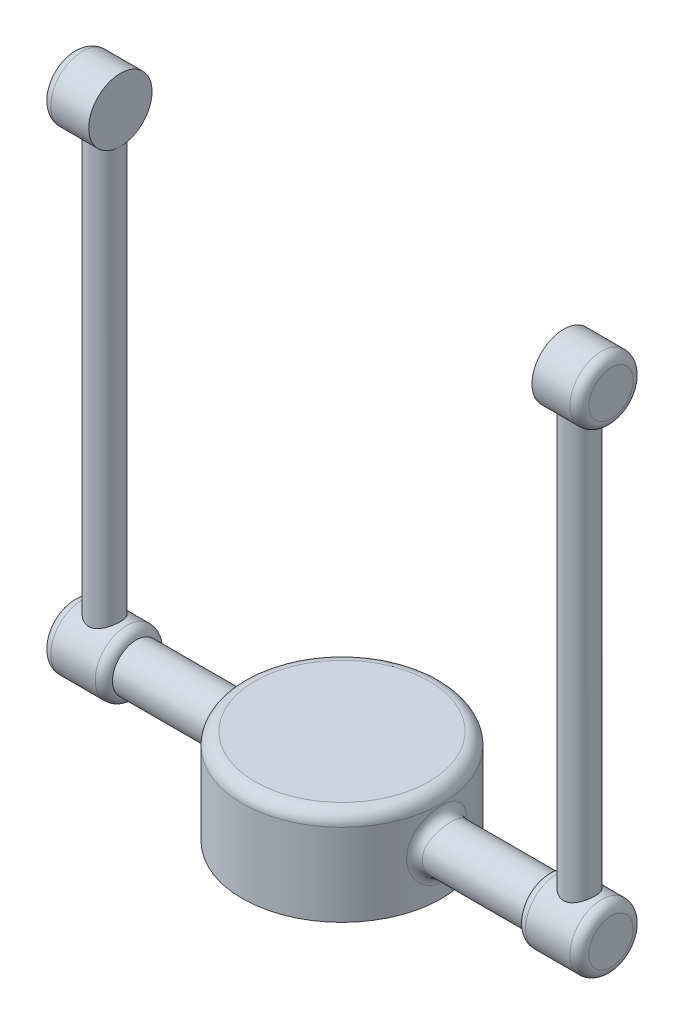
SolidWorks part; units mm, degrees
material "Polyester Resin"
ref_plane "Front Plane" through (0, 0, 0) normal (0, 0, 1) x (1, 0, 0)
ref_plane "Top Plane" through (0, 0, 0) normal (0, 1, 0) x (1, 0, 0)
ref_plane "Right Plane" through (0, 0, 0) normal (1, 0, 0) x (0, 0, -1)
sketch "Sketch1" plane through (0, 0, 0) normal (0, 1, 0) x (1, 0, 0)
  circle A0 centre (0, 0) radius 31.5
  dimension "D1" = 63
extrude "Boss-Extrude1" add sketch "Sketch1" along normal blind 30
sketch "Sketch2" plane through (0, 0, 0) normal (1, 0, 0) x (0, 0, -1)
  line L0 (0, 0) -> (0, 30) construction
  line L1 (31.5, 30) -> (-31.5, 30) construction
  circle A0 centre (0, 15) radius 7.5
  dimension "D1" = 15
extrude "Boss-Extrude2" add sketch "Sketch2" along normal blind 65
sketch "Sketch3" plane through (65, 0, 0) normal (1, 0, 0) x (0, 0, -1)
  circle A0 centre (0, 15) radius 10
  dimension "D1" = 20
extrude "Boss-Extrude3" add sketch "Sketch3" along normal blind 20
ref_axis "Axis1" through (0, 15, 0) along (1, 0, 0)
ref_plane "Plane1" through (0, 15, 0) normal (0, -1, 0) x (1, 0, 0)
sketch "Sketch4" plane through (0, 15, 0) normal (0, -1, 0) x (1, 0, 0)
  line L0 (0, 0) -> (65, 0) construction
  line L2 (65, 10) -> (65, -10) construction
  circle A0 centre (75, 0) radius 5
  dimension "D1" = 10
  dimension "D2" = 10
extrude "Boss-Extrude4" add sketch "Sketch4" against normal blind 150
sketch "Sketch5" plane through (85, 0, 0) normal (1, 0, 0) x (0, 0, -1)
  line L0 (0, 165) -> (0, 15) construction
  line L1 (5, 165) -> (-5, 165) construction
  circle A0 centre (0, 165) radius 10
  dimension "D1" = 20
extrude "Boss-Extrude5" add sketch "Sketch5" against normal blind 15
fillet "Fillet1" radius 3 4 edges at (30.6305, 16.492, -7.3501) (65, 15, -10) (85, 15, -10) (85, 165, -10)
mirror "Mirror1" about plane through (0, 0, 0) normal (1, 0, 0) of "Boss-Extrude5", "Boss-Extrude2", "Fillet1", "Boss-Extrude4", "Boss-Extrude3"
fillet "Fillet2" radius 4 1 edges at (0, 30, 31.5)
sketch "Sketch7" plane through (0, 0, 0) normal (0, 0, 1) x (1, 0, 0)
  line L0 (0, 0) -> (0, 10) construction
  line L2 (-12.5, 10) -> (12.5, 10) construction
  circle A1 centre (-12.5, 10) radius 4
  circle A2 centre (12.5, 10) radius 4
  point P6 (0, 10)
  dimension "D1" = 25
  dimension "D2" = 8
  dimension "D3" = 8
  dimension "D4" = 10
extrude "Boss-Extrude6" [suppressed] add sketch "Sketch7" along normal blind 80
sketch "Sketch8" [suppressed] plane through (0, 0, 80) normal (0, 0, 1) x (1, 0, 0)
  line L0 (-12.5, 10) -> (12.5, 10) construction
  line L1 (-20, 20) -> (20, 20)
  line L6 (-20, 20) -> (-20, -40)
  line L7 (-20, -40) -> (20, -40)
  line L8 (20, 20) -> (20, -40)
  line L9 (-20, 20) -> (20, -40) construction
  line L10 (-20, -40) -> (20, 20) construction
  line L11 (0, 20) -> (0, 10) construction
  line L12 (0, 20) -> (0, -3) construction
  circle A4 centre (0, -3) radius 2.555
  point P0 (0, -10)
  dimension "D5" = 23
  dimension "D4" = 5.11
  dimension "D1" = 10
  dimension "D2" = 60
  dimension "D3" = 40
extrude "Boss-Extrude7" [suppressed] add sketch "Sketch8" along normal blind 4
sketch "Sketch10" [suppressed] plane through (0, 20, 0) normal (0, 1, 0) x (1, 0, 0)
  line L0 (-20, -84) -> (-20, -80) construction
  line L1 (20, -80) -> (-20, -80)
  line L2 (20, -80) -> (20, -93)
  line L3 (20, -93) -> (-20, -93)
  line L4 (-20, -80) -> (-20, -93)
  dimension "D1" = 13
extrude "Boss-Extrude8" [suppressed] add sketch "Sketch10" along normal blind 3
sketch "Sketch11" [suppressed] plane through (0, -40, 0) normal (0, -1, 0) x (1, 0, 0)
  line L0 (-20, 84) -> (-20, 80) construction
  line L1 (20, 80) -> (-20, 80)
  line L2 (20, 80) -> (20, 93)
  line L3 (20, 93) -> (-20, 93)
  line L4 (-20, 80) -> (-20, 93)
  dimension "D1" = 13
extrude "Boss-Extrude9" [suppressed] add sketch "Sketch11" along normal blind 3
fillet "Fillet3" [suppressed] radius 5
fillet "Fillet4" [suppressed] radius 2
sketch "Sketch6" plane through (0, 0, 0) normal (0, -1, 0) x (1, 0, 0)
  circle A0 centre (0, 0) radius 29
  dimension "D1" = 58
extrude "Cut-Extrude1" cut sketch "Sketch6" against normal offset from surface (25 mm away) 5 up to face at (0, 30, 27.5)
chamfer "Chamfer1" distance 15 angle 45 1 edges at (0, 25, 29)
